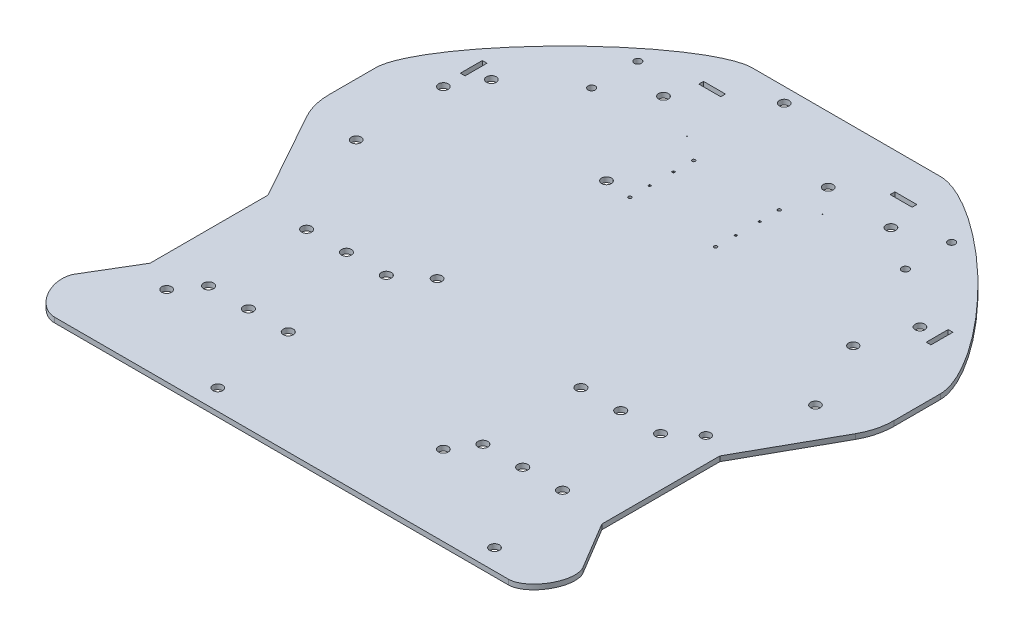
SolidWorks part; units mm, degrees
ref_plane "Front Plane" through (0, 0, 0) normal (0, 0, 1) x (1, 0, 0)
ref_plane "Top Plane" through (0, 0, 0) normal (0, 1, 0) x (1, 0, 0)
ref_plane "Right Plane" through (0, 0, 0) normal (1, 0, 0) x (0, 0, -1)
sketch "Sketch1" plane through (0, 0, 0) normal (0, 1, 0) x (1, 0, 0)
  line L0 (-90, 180) -> (-90, 0) construction
  line L1 (-180, 180) -> (0, 180)
  line L2 (-180, 180) -> (-180, 0)
  line L3 (-180, 0) -> (0, 0)
  line L4 (0, 180) -> (0, 0)
  line L5 (-180, 90) -> (0, 90) construction
  line L6 (-180, 30) -> (0, 30)
  line L7 (-130, 30) -> (-50, 30)
  line L8 (-130, 30) -> (-130, -30)
  line L9 (-130, -30) -> (-50, -30)
  line L10 (-50, 30) -> (-50, -30)
  line L11 (-130, 30) -> (-50, -30) construction
  line L12 (-130, -30) -> (-50, 30) construction
  dimension "D1" = 180
  dimension "D2" = 180
  dimension "D3" = 60
  dimension "D4" = 80
extrude "Boss-Extrude1" add sketch "Sketch1" along normal blind 1.6 contours L10 L3 L8 L9 | L2 L6 L4 L1 | L6 L10 L3 L4 | L8 L6 L2 L3 | L10 L6 L8 L3 region at (-90, 0, -105) region at (-155, 0, -15) region at (-25, 0, -15) region at (-90, 0, -15) region at (-90, 0, 15)
sketch "Sketch2" plane through (0, 1.6, 0) normal (0, 1, 0) x (1, 0, 0)
  line L0 (-180, 30) -> (0, 30)
  line L1 (-180, 180) -> (-180, 0) construction
  line L2 (0, 180) -> (0, 0) construction
  line L3 (-180, 180) -> (0, 180) construction
  line L4 (-90, 180) -> (-90, -30) construction
  line L5 (-130, -30) -> (-50, -30) construction
  dimension "D1" = 150
sketch "Sketch3" plane through (0, 1.6, 0) normal (0, 1, 0) x (1, 0, 0)
  line L0 (-180, 122) -> (0, 122)
  line L1 (-180, 180) -> (-180, 0) construction
  line L2 (0, 180) -> (0, 0) construction
  line L3 (-180, 30) -> (0, 30) construction
  dimension "D1" = 92
sketch "Sketch5" plane through (0, 1.6, 0) normal (0, 1, 0) x (1, 0, 0)
  line L0 (-114, 180) -> (-114, -30)
  line L1 (-180, 180) -> (0, 180) construction
  line L2 (-130, -30) -> (-50, -30) construction
  line L3 (-90, 180) -> (-90, -30) construction
  dimension "D1" = 24
fillet "Fillet1" radius 60 2 edges at (0, 0.8, -180) (-180, 0.8, -180) conic rho 0.2
sketch "Sketch6" plane through (0, 1.6, 0) normal (0, 1, 0) x (1, 0, 0)
  line L0 (-50, 0) -> (-130, 0)
  line L1 (-130, 0) -> (-130, -30)
  line L2 (-130, -30) -> (-50, -30)
  line L3 (-50, -30) -> (-50, 0)
  line L4 (-180, 0) -> (-162, 30.1113)
  line L5 (-162, 30.1113) -> (-162, 67.7113)
  line L6 (-162, 67.7113) -> (-180, 100)
  line L7 (-180, 120) -> (-180, 0) construction
  line L8 (-90, 180) -> (-90, -30) construction
  line L10 (-90, 180) -> (-90, 0) construction
  line L11 (0, 0) -> (-18, 30.1113)
  line L12 (-18, 30.1113) -> (-18, 67.7113)
  line L13 (-18, 67.7113) -> (0, 100)
  line M3 (0, 0) -> (0, 120)
  line M7 (-180, 120) -> (-180, 0)
  line M9 (-130, 0) -> (-130, -30)
  line M10 (-130, -30) -> (-50, -30)
  line M11 (-50, -30) -> (-50, 0)
  dimension "D1" = 37.6
  dimension "D2" = 72
  dimension "D3" = 100
extrude "Cut-Extrude1" cut sketch "Sketch6" against normal blind 10 contours L0 M11 M9 M10 | L5 L6 L4 M7 | L13 L12 L11 M3 region at (-90, 1.6, 15) region at (-172.3605, 1.6, -49.5379) region at (-7.6395, 1.6, -49.5379)
fillet "Fillet2" radius 10 2 edges at (-180, 0.8, 0) (0, 0.8, 0) conic rho 0.25
fillet "Fillet3" radius 20 2 edges at (-180, 0.8, -100) (0, 0.8, -100)
sketch "Sketch8" plane through (0, 1.6, 0) normal (0, 1, 0) x (1, 0, 0)
  line L1 (-63, 168.5) -> (-56, 168.5)
  line L2 (-63, 168.5) -> (-63, 167)
  line L3 (-63, 167) -> (-56, 167)
  line L4 (-56, 168.5) -> (-56, 167)
  line L5 (-117, 168.5) -> (-124, 168.5)
  line L6 (-117, 168.5) -> (-117, 167)
  line L7 (-117, 167) -> (-124, 167)
  line L8 (-124, 168.5) -> (-124, 167)
  line L9 (-165, 139) -> (-163.5, 139)
  line L10 (-165, 139) -> (-165, 132)
  line L11 (-165, 132) -> (-163.5, 132)
  line L12 (-163.5, 139) -> (-163.5, 132)
  line L13 (-16.5, 139) -> (-15, 139)
  line L14 (-16.5, 139) -> (-16.5, 132)
  line L15 (-16.5, 132) -> (-15, 132)
  line L16 (-15, 139) -> (-15, 132)
  circle A4 centre (-105.105, 175.3311) radius 1.55
  circle A5 centre (-74.9002, 159.1312) radius 1.55
  circle A8 centre (-112, 125.592) radius 1.55
  circle A9 centre (-164, 125.592) radius 1.55
  circle A10 centre (-112, 71.592) radius 1.55
  circle A11 centre (-146.4125, 64.417) radius 1.5875
  circle A12 centre (-133.7125, 64.417) radius 1.5875
  circle A13 centre (-121.0125, 64.417) radius 1.5875
  circle A14 centre (-146.4125, 33.175) radius 1.5875
  circle A15 centre (-133.7125, 33.175) radius 1.5875
  circle A16 centre (-121.0125, 33.175) radius 1.5875
  circle A17 centre (-58.9875, 64.417) radius 1.5875
  circle A18 centre (-46.2875, 64.417) radius 1.5875
  circle A19 centre (-33.5875, 64.417) radius 1.5875
  circle A20 centre (-33.5875, 33.175) radius 1.5875
  circle A21 centre (-46.2875, 33.175) radius 1.5875
  circle A22 centre (-58.9875, 33.175) radius 1.5875
  circle A23 centre (-63.9, 25.5) radius 1.55
  circle A24 centre (-28.6, 6.5) radius 1.55
  circle A25 centre (-116.8, 6.5) radius 1.55
  circle A26 centre (-152.1, 25.5) radius 1.55
  circle A27 centre (-27.14, 119.392) radius 1.5
  circle A28 centre (-25.87, 71.132) radius 1.5
  dimension "D3" = 3.1
  dimension "D4" = 3.1
  dimension "D5" = 3.1
  dimension "D6" = 3.1
  dimension "D7" = 3.1
  dimension "D8" = 3.175
  dimension "D9" = 3.175
  dimension "D10" = 3.175
  dimension "D11" = 3.175
  dimension "D12" = 3.175
  dimension "D13" = 3.175
  dimension "D14" = 3.1
  dimension "D15" = 3.1
  dimension "D16" = 3.1
  dimension "D17" = 3.1
  dimension "D18" = 3.175
  dimension "D19" = 3.175
  dimension "D20" = 3.175
  dimension "D21" = 3.175
  dimension "D22" = 3.175
  dimension "D23" = 3.175
  dimension "D24" = 3
  dimension "D25" = 3
extrude "Cut-Extrude2" cut sketch "Sketch8" against normal up to next (1.6 mm away)
sketch "Sketch9" plane through (0, 0, 0) normal (0, -1, 0) x (1, 0, 0)
  line L1 (-68.18, -150.89) -> (-68.42, -150.89)
  line L2 (-68.18, -150.89) -> (-68.18, -150.65)
  line L3 (-68.18, -150.65) -> (-68.42, -150.65)
  line L4 (-68.42, -150.89) -> (-68.42, -150.65)
  line L5 (-111.36, -150.89) -> (-111.6, -150.89)
  line L6 (-111.36, -150.89) -> (-111.36, -150.65)
  line L7 (-111.36, -150.65) -> (-111.6, -150.65)
  line L8 (-111.6, -150.89) -> (-111.6, -150.65)
  line L9 (-76.01, -139.0625) -> (-76.645, -139.0625)
  line L10 (-76.01, -139.0625) -> (-76.01, -138.4275)
  line L11 (-76.01, -138.4275) -> (-76.645, -138.4275)
  line L12 (-76.645, -139.0625) -> (-76.645, -138.4275)
  line L13 (-76.01, -131.4425) -> (-76.645, -131.4425)
  line L14 (-76.01, -131.4425) -> (-76.01, -130.8075)
  line L15 (-76.01, -130.8075) -> (-76.645, -130.8075)
  line L16 (-76.645, -131.4425) -> (-76.645, -130.8075)
  line L17 (-103.47, -139.0625) -> (-104.105, -139.0625)
  line L18 (-103.47, -139.0625) -> (-103.47, -138.4275)
  line L19 (-103.47, -138.4275) -> (-104.105, -138.4275)
  line L20 (-104.105, -139.0625) -> (-104.105, -138.4275)
  line L21 (-103.47, -131.4425) -> (-104.105, -131.4425)
  line L22 (-103.47, -131.4425) -> (-103.47, -130.8075)
  line L23 (-103.47, -130.8075) -> (-104.105, -130.8075)
  line L24 (-104.105, -131.4425) -> (-104.105, -130.8075)
  circle A0 centre (-163.2, -97) radius 1.55
  circle A1 centre (-158.3, -135.2) radius 1.55
  circle A2 centre (-126.25, -158) radius 1.55
  circle A3 centre (-53.75, -158) radius 1.55
  circle A4 centre (-21.7, -135.2) radius 1.55
  circle A5 centre (-16.8, -97) radius 1.55
  circle A6 centre (-76.405, -124.775) radius 0.5
  circle A7 centre (-103.71, -145.095) radius 0.5
  circle A8 centre (-76.405, -145.095) radius 0.5
  circle A9 centre (-103.71, -124.775) radius 0.5
  circle A10 centre (-140, -148.857) radius 1.143
  circle A11 centre (-140, -163.589) radius 1.143
  circle A12 centre (-40, -148.857) radius 1.143
  circle A13 centre (-40, -163.589) radius 1.143
  dimension "D1" = 3.1
  dimension "D2" = 3.1
  dimension "D3" = 3.1
  dimension "D4" = 3.1
  dimension "D5" = 3.1
  dimension "D6" = 3.1
  dimension "D7" = 1
  dimension "D8" = 1
  dimension "D9" = 1
  dimension "D10" = 1
  dimension "D11" = 2.286
  dimension "D12" = 2.286
  dimension "D13" = 2.286
  dimension "D14" = 2.286
extrude "Cut-Extrude3" cut sketch "Sketch9" against normal up to next
